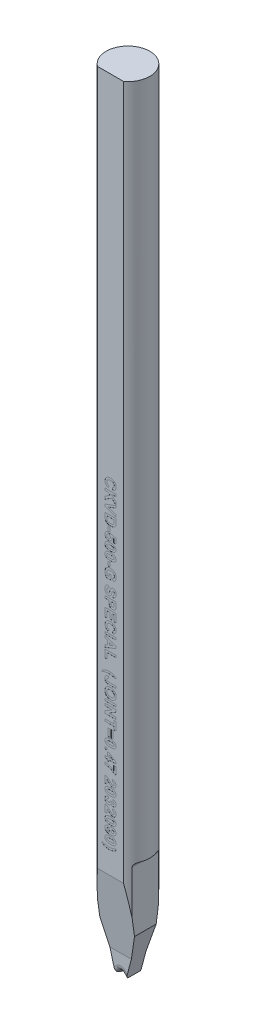
SolidWorks part; units mm, degrees
ref_plane "Ebene vorne" through (0, 0, 0) normal (0, 0, 1) x (1, 0, 0)
ref_plane "Ebene oben" through (0, 0, 0) normal (0, 1, 0) x (1, 0, 0)
ref_plane "Ebene rechts" through (0, 0, 0) normal (1, 0, 0) x (0, 0, -1)
sketch "sketch_TL_cutting" plane through (0, 0, 0) normal (0, 1, 0) x (1, 0, 0)
  circle A0 centre (0, 0) radius 1.9977
extrude "TL_cutting" add sketch "sketch_TL_cutting" along normal blind 72.009
sketch "sketch_TDF_grinding" plane through (0, 0, 0) normal (0, 1, 0) x (1, 0, 0)
  line L0 (0, 0) -> (0, -1.6015) construction
  line L1 (-2.0077, -5.6169) -> (2.0077, -5.6169)
  line L2 (-2.0077, -5.6169) -> (-2.0077, -1.6015)
  line L3 (-2.0077, -1.6015) -> (2.0077, -1.6015)
  line L4 (2.0077, -5.6169) -> (2.0077, -1.6015)
  circle A1 centre (0, 0) radius 1.9977 construction
  point P9 (0, -5.6169)
  dimension "TD_2Offset_X" = 4.0154
  dimension "TD_2Offset_Z" = 4.0154
extrude "TDF_grinding" cut sketch "sketch_TDF_grinding" along normal through all
sketch "sketch_engraving" plane through (0, 0, 1.6015) normal (0, 0, 1) x (1, 0, 0)
  line L0 (1.1942, 72.009) -> (-1.1942, 72.009) construction
  line L6 (-1.1942, 0) -> (1.1942, 0) construction
  line L7 (0, 0) -> (0, 40.009) construction
  line L8 (-0.5, 40.009) -> (-0.5, 0) construction
  text T0 "CKVD-500-G SPECIAL  (JOINT=0.47 2032090)" font "Arial" height 1
  dimension "D2" = 0.5
  dimension "EngravingStart" = 32
extrude "engraving" cut sketch "sketch_engraving" against normal blind 0.005
sketch "sketch_VW_VR_grinding" plane through (0, 0, 0) normal (0, 0, 1) x (1, 0, 0)
  line L0 (-1.59, -0.01) -> (-1.59, 9.682)
  line L1 (1.59, -0.01) -> (1.59, 9.682)
  line L2 (-1.59, 0) -> (1.59, 0) construction
  line L3 (-2.0077, 10) -> (-1.908, 10)
  line L4 (1.908, 10) -> (2.0077, 10)
  line L5 (-2.0077, 10) -> (-2.0077, -0.01)
  line L6 (-2.0077, -0.01) -> (-1.59, -0.01)
  line L7 (1.59, -0.01) -> (2.0077, -0.01)
  line L8 (2.0077, -0.01) -> (2.0077, 10)
  line L9 (-1.908, 10) -> (-1.908, 9.682) construction
  line L10 (-1.59, 9.682) -> (-1.908, 9.682) construction
  line L11 (1.59, 9.682) -> (1.908, 9.682) construction
  line L12 (1.908, 10) -> (1.908, 9.682) construction
  arc A0 (-1.908, 10) -> (-1.59, 9.682) centre (-1.908, 9.682) cw
  arc A2 (1.59, 9.682) -> (1.908, 10) centre (1.908, 9.682) cw
  dimension "D2" = 0.318
  dimension "D1" = 0.01
  dimension "D4" = 4.0154
extrude "VW_VR_grinding" cut sketch "sketch_VW_VR_grinding" against normal blind 2.0077 and the other way blind 2.0077
sketch "sketch_ISA_grinding" plane through (0, 0, 0) normal (0, 0, 1) x (1, 0, 0)
  line L0 (-0.5004, 0) -> (-2.0077, 5.6254)
  line L4 (2.0077, 5.6254) -> (0.5004, 0)
  line L5 (0.5004, 0) -> (-0.5004, 0)
  line L6 (0, 0) -> (0, 30.49) construction
  line L7 (-2.0077, 5.6254) -> (-2.0077, -0.01)
  line L12 (-2.0077, -0.01) -> (2.0077, -0.01)
  line L13 (2.0077, -0.01) -> (2.0077, 5.6254)
  dimension "ISA" = 30
  dimension "TD_2Offset" = 4.0154
  dimension "Offset" = 0.01
extrude "ISA_grinding" cut sketch "sketch_ISA_grinding" against normal blind 2.0077 and the other way blind 2.0077
sketch "sketch_pre_FRX_BRX" plane through (0, 0, 0) normal (1, 0, 0) x (0, 0, -1)
  line L0 (1.9977, -0.01) -> (1.9977, 3.9152) construction
  line L1 (-1.6015, -0.01) -> (-1.6015, 1.7909) construction
  line L2 (-0.6744, -0.01) -> (-0.6744, 1.7909)
  line L3 (-0.6744, 1.7909) -> (-2.0077, 1.7909)
  line L4 (-2.0077, 1.7909) -> (-2.0077, -0.01)
  line L5 (-2.0077, -0.01) -> (-0.6744, -0.01)
  line L6 (0.6744, -0.01) -> (0.6744, 1.7909)
  line L7 (0.6744, 1.7909) -> (2.0077, 1.7909)
  line L8 (2.0077, 1.7909) -> (2.0077, -0.01)
  line L9 (2.0077, -0.01) -> (0.6744, -0.01)
  dimension "D3" = 0.01
  dimension "D4" = 1.8009
  dimension "D5" = 4.0154
  dimension "D6" = 1.3487
  dimension "D2" = 0.01
  dimension "D7" = 2.6721
extrude "pre_FRX_BRX" cut sketch "sketch_pre_FRX_BRX" against normal blind 2.0077 and the other way blind 2.0077
sketch "sketch_contour_V-Groove" plane through (0, 0, 0) normal (1, 0, 0) x (0, 0, -1)
  line L0 (-1.6015, 0.2845) -> (0, 0.2845)
  line L1 (0, 0.2845) -> (1.9977, 0.2845)
  line L2 (1.9977, -0.8411) -> (1.9977, 1.3178) construction
  line L3 (-1.6015, -0.9209) -> (-1.6015, 1.9363) construction
  line L4 (-1.6015, 0) -> (1.9977, 0) construction
  line L5 (0.6744, 0) -> (0.6744, 0.2845) construction
  line L6 (-0.6744, 0) -> (-0.6744, 0.2845) construction
  dimension "D1" = 0
ref_plane "front" through (0, 0, 1.6015) normal (0, 0, 1) x (1, 0, 0)
ref_plane "back" through (0, 0, -1.9977) normal (0, 0, 1) x (1, 0, 0)
sketch "sketch_section_V-Groove" plane through (0, 0, 1.6015) normal (0, 0, 1) x (1, 0, 0)
  line L0 (-3.1496, -2.8448) -> (-0.0347, 0.2701)
  line L2 (0.0347, 0.2701) -> (3.1496, -2.8448)
  line L3 (-3.1496, -2.8448) -> (3.1496, -2.8448)
  line L4 (0, -2.8448) -> (0, 0.2845) construction
  line L5 (-0.3048, 0) -> (0.3048, 0) construction
  arc A0 (0.0347, 0.2701) -> (-0.0347, 0.2701) centre (0, 0.2354) ccw
  dimension "GA" = 90
sweep "V-Groove_EDM" cut profiles "sketch_section_V-Groove" path "sketch_contour_V-Groove"
fillet "FR_EDM" radius 0.5004 3 edges at (0.1697, 0.1351, 0.6744) (0, 0.2845, 0.6744) (-0.1697, 0.1351, 0.6744)
fillet "BR_EDM" radius 0.2489 3 edges at (0.1697, 0.1351, -0.6744) (0, 0.2845, -0.6744) (-0.1697, 0.1351, -0.6744)
sketch "sketch_FA_BA_grinding" plane through (0, 0, 0) normal (1, 0, 0) x (0, 0, -1)
  line L2 (2.9977, 18.3323) -> (2.9977, -0.1)
  line L3 (2.9977, -0.1) -> (0.6744, -0.1)
  line L5 (0.6744, -0.1) -> (0.6744, 1.8009)
  line L6 (0.6744, 1.8009) -> (2.9977, 18.3323)
  line L7 (1.9977, -0.1) -> (1.9977, 11.2169) construction
  line L8 (-1.6015, 8.3975) -> (-1.6015, -0.1) construction
  line L9 (-3.6221, 22.7749) -> (-0.6744, 1.8009)
  line L10 (-0.6744, 1.8009) -> (-0.6744, -0.1)
  line L11 (-0.6744, -0.1) -> (-3.6221, -0.1)
  line L12 (-3.6221, -0.1) -> (-3.6221, 22.7749)
  line L13 (-0.6744, 1.8009) -> (0.6744, 1.8009) construction
  dimension "D4" = 1
  dimension "D1" = 0.1
  dimension "FA" = 8
  dimension "BA" = 8
extrude "FA_BA_grinding" cut sketch "sketch_FA_BA_grinding" against normal blind 2.0077 and the other way blind 2.0077
sketch "sketch_groove_dimensions" plane through (0, 0, 0) normal (1, 0, 0) x (0, 0, -1)
  line L0 (-0.174, 0.2845) -> (0.4255, 0.2845)
  line L1 (-0.6744, 0) -> (-0.6744, 0.7849) construction
  line L2 (1.9977, 0) -> (1.9977, 0.4166) construction
  line L3 (0.6744, 0) -> (0.6744, 0.5334) construction
  line L4 (-1.6015, 0) -> (-1.6015, 0.3999) construction
  arc A0 (0.4255, 0.2845) -> (0.6744, 0.5334) centre (0.4255, 0.5334) ccw
  arc A1 (-0.174, 0.2845) -> (-0.6744, 0.7849) centre (-0.174, 0.7849) cw
equation "\"_Offset\"=0.01mm"
equation "\"TL\"=72.009mm"
equation "\"TD\"=3.99542mm"
equation "\"TDF\"=3.59918mm"
equation "\"BA\"=8deg"
equation "\"ISA\"=30deg"
equation "\"FA\"=8deg"
equation "\"GR\"=0.0508mm"
equation "\"GA\"=90deg"
equation "\"GD\"=0.28448mm"
equation "\"FL\"=1.34874mm"
equation "\"F\"=0.59944mm"
equation "\"FX\"=0mm"
equation "\"B\"=0.6096mm"
equation "\"VW\"=3.18008mm"
equation "\"cleaned_VR\"= IIF ( \"VR\" > 0 , \"VR\" , \"E\" - \"_Offset\" )"
equation "\"cleaned_VW\"= IIF ( \"VW\" > 0 , \"VW\" , \"TD\" - \"_Offset\" )"
equation "\"back_edge\"= \"TD\" / 2 - \"X\""
equation "\"side_edge_Offset\"= \"TD\" / 2 + \"_Offset\""
equation "\"TD@sketch_TL_cutting\"=\"TD\""
equation "\"TL@TL_cutting\"=\"TL\""
equation "\"TDF@sketch_TDF_grinding\"=\"TDF\""
equation "\"TD_2Offset_X@sketch_TDF_grinding\"=\"TD\"+2*\"_Offset\""
equation "\"TD_2Offset_Z@sketch_TDF_grinding\"=\"TD\"+2*\"_Offset\""
equation "\"TL_Offset\"= \"TL\" + \"_Offset\""
equation "\"ISA@sketch_ISA_grinding\"=\"ISA\""
equation "\"W@sketch_ISA_grinding\"=\"W\""
equation "\"TD_2Offset@sketch_ISA_grinding\"=\"TD\"+2*\"_Offset\""
equation "\"Offset@sketch_ISA_grinding\"=\"_Offset\""
equation "\"05TD_Offset_posZ@ISA_grinding\"=\"side_edge_Offset\""
equation "\"05TD_Offset_negZ@ISA_grinding\"=\"side_edge_Offset\""
equation "\"E\"=1.80086mm"
equation "\"cleaned_X\"= IIF ( \"X\" > 0 , \"X\" , \"TD\" / 2 - \"FL\" / 2 )"
equation "\"FR\"=0.50038mm"
equation "\"BR\"=0.24892mm"
equation "\"D1\"= \"side_edge_Offset\""
equation "\"D2\"= \"side_edge_Offset\""
equation "\"TDF@sketch_FA_BA_grinding\" = \"TDF\""
equation "\"FL@sketch_FA_BA_grinding\"=\"FL\""
equation "\"E@sketch_FA_BA_grinding\" = \"E\""
equation "\"D1@FA_BA_grinding\"=\"side_edge_Offset\""
equation "\"D2@FA_BA_grinding\"=\"side_angle_Offset\""
equation "\"10GD@sketch_section_V-Groove\" = 10 * \"GD\""
equation "\"GA@sketch_section_V-Groove\" = \"GA\""
equation "\"GD@sketch_section_V-Groove\" = \"GD\""
equation "\"B@sketch_section_V-Groove\" = \"B\""
equation "\"GD@sketch_contour_V-Groove\" = \"GD\""
equation "\"cleaned_FRX\"= IIF ( \"FRX\" > 0 , \"FRX\" , \"FR\" )"
equation "\"cleaned_BRX\"= IIF ( \"BRX\" > 0 , \"BRX\" , \"BR\" )"
equation "\"FL_groove_angle\"=0deg"
equation "\"D3@sketch_pre_FRX_BRX\" = \"_Offset\""
equation "\"D4@sketch_pre_FRX_BRX\" = \"E\""
equation "\"D5@sketch_pre_FRX_BRX\" = 2 * \"side_edge_Offset\""
equation "\"D6@sketch_pre_FRX_BRX\" = \"FL\" + ( \"FR\" - \"cleaned_FRX\" ) + ( \"BR\" - \"cleaned_BRX\" )"
equation "\"TD/2@sketch_pre_FRX_BRX\" = \"TD\" / 2"
equation "\"TDF@sketch_pre_FRX_BRX\" = \"TDF\""
equation "\"D2@sketch_pre_FRX_BRX\" = \"_Offset\""
equation "\"D1@pre_FRX_BRX\" = \"side_edge_Offset\""
equation "\"D2@pre_FRX_BRX\" = \"side_edge_Offset\""
equation "\"D1@BR_EDM\"=\"BR\""
equation "\"TD/2@sketch_FA_BA_grinding\" = \"TD\" / 2"
equation "\"TD/2@sketch_contour_V-Groove\" = \"TD\" / 2"
equation "\"TDF@sketch_contour_V-Groove\" = \"TDF\""
equation "\"D1@sketch_contour_V-Groove\"=\"FL_groove_angle\""
equation "\"FL@sketch_contour_V-Groove\"=\"FL\""
equation "\"FL/2@sketch_contour_V-Groove\" = \"FL\" / 2"
equation "\"D1@FR_EDM\"=\"FR\""
equation "\"D1@sketch_VW_VR_grinding\" = \"_Offset\""
equation "\"D4@sketch_VW_VR_grinding\" = 2 * \"side_edge_Offset\""
equation "\"VR@sketch_VW_VR_grinding\" = \"cleaned_VR\""
equation "\"VW@sketch_VW_VR_grinding\"=\"cleaned_VW\""
equation "\"D1@VW_VR_grinding\" = \"side_edge_Offset\""
equation "\"D2@VW_VR_grinding\" = \"side_edge_Offset\""
equation "\"X\"=0.94996mm"
equation "\"VR\"=9.99998mm"
equation "\"W\"=1.00076mm"
equation "\"VW_radius\"= \"cleaned_VW\" / 10"
equation "\"VW_radius_cleaned\"= IIF ( \"VW\" > 0 , \"VW_radius\" , \"_Offset\" / 2 )"
equation "\"D2@sketch_VW_VR_grinding\"=\"VW_radius_cleaned\""
equation "\"FRX\"=0mm"
equation "\"BRX\"=0mm"
equation "\"FA@sketch_FA_BA_grinding\" = \"FA\""
equation "\"D4@sketch_FA_BA_grinding\"=\"_Offset\"*100"
equation "\"BA@sketch_FA_BA_grinding\" = \"BA\""
equation "\"D1@sketch_groove_dimensions\" = \"TD\" / 2"
equation "\"FL@sketch_groove_dimensions\" = \"FL\""
equation "\"FR@sketch_groove_dimensions\" = \"FR\""
equation "\"BR@sketch_groove_dimensions\" = \"BR\""
equation "\"FRX@sketch_groove_dimensions\" = \"cleaned_FRX\""
equation "\"BRX@sketch_groove_dimensions\" = \"cleaned_BRX\""
equation "\"GD@sketch_groove_dimensions\" = \"GD\""
equation "\"cleaned_FX\"= IIF ( \"FX\" > 0 , \"FX\" , \"TDF\" - ( \"TD\" + \"FL\" ) / 2 )"
equation "\"D7@sketch_pre_FRX_BRX\"=\"TDF\"-\"cleaned_FX\"-(\"FR\"-\"cleaned_FRX\")"
equation "\"FX@sketch_contour_V-Groove\" = \"cleaned_FX\""
equation "\"FX@sketch_FA_BA_grinding\" = \"cleaned_FX\""
equation "\"TDF@sketch_groove_dimensions\" = \"TDF\""
equation "\"FX@sketch_groove_dimensions\" = \"cleaned_FX\""
equation "\"EngravingStart\"=32mm"
equation "\"EngravingStart@sketch_engraving\" = \"EngravingStart\""
